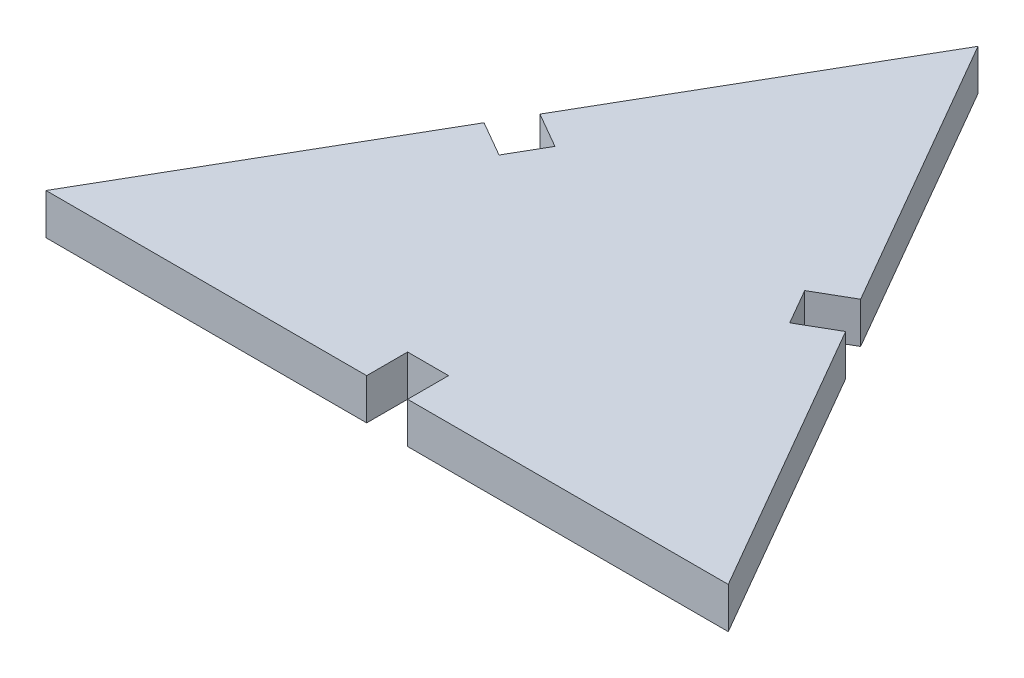
SolidWorks part; units mm, degrees
ref_plane "Front Plane" through (0, 0, 0) normal (0, 0, 1) x (1, 0, 0)
ref_plane "Top Plane" through (0, 0, 0) normal (0, 1, 0) x (1, 0, 0)
ref_plane "Right Plane" through (0, 0, 0) normal (1, 0, 0) x (0, 0, -1)
sketch "Sketch1" plane through (0, 0, 0) normal (0, 1, 0) x (1, 0, 0)
  line L0 (0.4808, 26.5344) -> (-24.5192, -16.7668)
  line L1 (-24.5192, -16.7668) -> (25.4808, -16.7668)
  line L2 (25.4808, -16.7668) -> (0.4808, 26.5344)
  dimension "D1" = 50
extrude "Boss-Extrude1" add sketch "Sketch1" along normal blind 3
sketch "Sketch3" plane through (0, 3, 0) normal (0, 1, 0) x (1, 0, 0)
  line L0 (-12.0192, 4.8838) -> (25.4808, -16.7668) construction
  line L1 (0.4808, 26.5344) -> (-24.5192, -16.7668) construction
  line L2 (-24.5192, -16.7668) -> (12.9808, 4.8838) construction
  line L3 (25.4808, -16.7668) -> (0.4808, 26.5344) construction
  line L4 (0.4808, 26.5344) -> (0.4808, -16.7668) construction
  line L5 (-24.5192, -16.7668) -> (25.4808, -16.7668) construction
  line L6 (-12.7692, 3.5848) -> (-10.1712, 2.0848)
  line L7 (-10.1712, 2.0848) -> (-8.6712, 4.6828)
  line L8 (-11.2692, 6.1828) -> (-8.6712, 4.6828)
  line L9 (13.7308, 3.5848) -> (11.1327, 2.0848)
  line L10 (9.6327, 4.6828) -> (11.1327, 2.0848)
  line L11 (12.2308, 6.1828) -> (9.6327, 4.6828)
  line L12 (-1.0192, -16.7668) -> (-1.0192, -13.7668)
  line L13 (1.9808, -13.7668) -> (-1.0192, -13.7668)
  line L14 (1.9808, -16.7668) -> (1.9808, -13.7668)
  line L15 (-12.7692, 3.5848) -> (-11.2692, 6.1828)
  line L16 (12.2308, 6.1828) -> (13.7308, 3.5848)
  line L17 (1.9808, -16.7668) -> (-1.0192, -16.7668)
  point P18 (0.4808, -2.3331)
  point P20 (-9.4212, 3.3838)
  point P32 (0.4808, -2.3331)
  dimension "D1" = 3
  dimension "D2" = 3
  dimension "D3" = 3
extrude "Cut-Extrude1" cut sketch "Sketch3" against normal up to next
equation "\"D1@Boss-Extrude1\"=\"T@d20.Assembly\""
